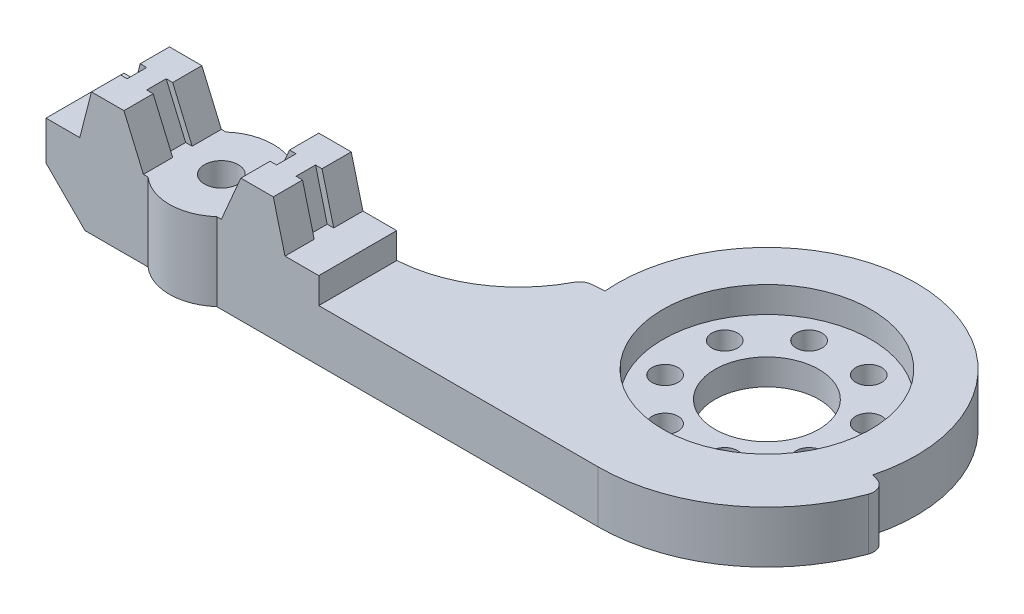
SolidWorks part; units mm, degrees
material "ABS"
ref_plane "正面" through (0, 0, 0) normal (0, 0, 1) x (1, 0, 0)
ref_plane "平面" through (0, 0, 0) normal (0, 1, 0) x (1, 0, 0)
ref_plane "右側面" through (0, 0, 0) normal (1, 0, 0) x (0, 0, -1)
sketch "ｽｹｯﾁ1" plane through (0, 0, 0) normal (0, 1, 0) x (1, 0, 0)
  line L0 (19, 10) -> (19, 3)
  line L1 (-10.5, 3) -> (32, 3)
  line L2 (-10.5, 3) -> (-10.5, -3)
  line L3 (-10.5, -3) -> (32, -3)
  line L4 (32, 3) -> (32, -3)
  line L5 (-10.5, 3) -> (32, -3) construction
  line L6 (-10.5, -3) -> (32, 3) construction
  line L7 (32, 10) -> (19.0495, 8.867)
  line L8 (32, 10) -> (44.557, 6.6354)
  line L9 (19.0495, 8.867) -> (17.1765, 8.7031)
  circle A0 centre (32, 10) radius 13
  circle A1 centre (32, 10) radius 11.5
  point P4 (10.75, 0)
  dimension "D5" = 26
  dimension "D6" = 23
  dimension "D1" = 6
  dimension "D2" = 3
  dimension "D3" = 10.5
  dimension "D4" = 32
  dimension "D7" = 5
  dimension "D8" = 15
extrude "ﾎﾞｽ - 押し出し1" add sketch "ｽｹｯﾁ1" along normal blind 4 contours A0 L1 L2 L3 | A0 L9 L0 L1 | A1 L7 A0 L1 | L4 A1 L8 L7 L1 | L8 A1 L7 | L1 A1 L4 | A1 L1 A0 L4 | A1 L4 A0 L8 region at (19.6068, 0, -4.7032) region at (20.6203, 0, -5.8719) region at (6.9791, 0, 0.1211) region at (39.8161, 0, 0.1861) region at (32.377, 0, -14.3095) region at (32.0912, 0, -5.2465) region at (26.5286, 0, 0.4611) region at (28.4673, 0, -1.1659)
fillet "ﾌｨﾚｯﾄ1" radius 10 1 edges at (19, 2, -3)
fillet "ﾌｨﾚｯﾄ2" radius 1 2 edges at (44.557, 2, -6.6354) (19, 2, -8.8626)
sketch "ｽｹｯﾁ2" plane through (0, 4, 0) normal (0, 1, 0) x (1, 0, 0)
  line L0 (-10.5, 3) -> (9.896, 3) construction
  line L1 (-10.5, -3) -> (10.5, -3)
  line L2 (-10.5, -3) -> (-10.5, 3)
  line L3 (-10.5, 3) -> (10.5, 3)
  line L4 (10.5, -3) -> (10.5, 3)
  line L5 (-10.5, -3) -> (10.5, 3) construction
  line L6 (-10.5, 3) -> (10.5, -3) construction
  point P4 (0, 0)
  dimension "D1" = 21
extrude "ﾎﾞｽ - 押し出し2" add sketch "ｽｹｯﾁ2" along normal blind 2
sketch "ｽｹｯﾁ3" plane through (0, 6, 0) normal (0, 1, 0) x (1, 0, 0)
  circle A0 centre (0, 0) radius 4
  dimension "D1" = 8
extrude "ﾎﾞｽ - 押し出し3" add sketch "ｽｹｯﾁ3" against normal up to surface (6 mm away) up to face at (21.4165, 0, -5.634)
hole_wizard "M2 丸平ねじ用座ぐり穴1" positions "ｽｹｯﾁ4" profile "ｽｹｯﾁ5" counterbore size "M2" standard "JIS" end condition up to next
sketch "ｽｹｯﾁ4" plane through (0, 0, 0) normal (0, -1, 0) x (-1, 0, 0)
  point P0 (0, 0)
sketch "ｽｹｯﾁ5" plane through (0, 0, 0) normal (1, 0, 0) x (0, 0, -1)
  line L0 (0, 0) -> (0, 6)
  line L1 (0, 6) -> (1.3, 6)
  line L3 (1.3, 6) -> (1.3, 2)
  line L4 (1.3, 2) -> (3.1, 2)
  line L5 (3.1, 2) -> (3.1, 0)
  line L7 (3.1, 0) -> (0, 0)
  line L11 (0, -6.35) -> (0, 107.95) construction
  dimension "通し穴の直径" = 2.6
  dimension "通し穴の深さ" = 6
  dimension "座ぐり穴の直径" = 6.2
  dimension "座ぐり穴の深さ" = 2
chamfer "面取り1" distance 3 angle 45 1 edges at (-10.5, 0, 0)
sketch "ｽｹｯﾁ6" plane through (0, 0, 3) normal (0, 0, 1) x (1, 0, 0)
  line L0 (3, 6) -> (4.5, 9.5)
  line L1 (2.6458, 6) -> (10.5, 6) construction
  line L2 (4.5, 9.5) -> (7, 9.5)
  line L3 (7, 9.5) -> (7.9, 6)
  line L4 (7.9, 6) -> (3, 6)
  dimension "D1" = 3.5
  dimension "D2" = 3
  dimension "D3" = 2.5
  dimension "D4" = 7
  dimension "D5" = 7.9
extrude "ﾎﾞｽ - 押し出し4" add sketch "ｽｹｯﾁ6" against normal up to surface (6 mm away) up to face at (7.6806, 3.3333, -3)
sketch "ｽｹｯﾁ10" plane through (0, 0, 0) normal (0, 0, 1) x (1, 0, 0)
  line L0 (5, 9.5) -> (4.5, 9.5)
  line L1 (5, 9.5) -> (3.5, 6)
  line L2 (4.5, 9.5) -> (3, 6)
  line L3 (3.5, 6) -> (3, 6)
  line L4 (5, 9.5) -> (3, 6) construction
  line L5 (4.5, 9.5) -> (3.5, 6) construction
  line L6 (7, 9.5) -> (4.5, 9.5) construction
  line L7 (6.5, 9.5) -> (7, 9.5)
  line L8 (6.5, 9.5) -> (7.4, 6)
  line L9 (7, 9.5) -> (7.9, 6)
  line L10 (7.4, 6) -> (7.9, 6)
  line L11 (6.5, 9.5) -> (7.9, 6) construction
  line L12 (7, 9.5) -> (7.4, 6) construction
  point P5 (4, 7.75)
  point P14 (7.2, 7.75)
  dimension "D1" = 0.5
extrude "ｶｯﾄ - 押し出し2" cut sketch "ｽｹｯﾁ10" against normal mid plane 1.5
mirror "ﾐﾗｰ1" about plane through (0, 0, 0) normal (1, 0, 0) of "ｶｯﾄ - 押し出し2", "ﾎﾞｽ - 押し出し4"
hole_wizard "M2 丸平ねじ用座ぐり穴2" positions "ｽｹｯﾁ7" profile "ｽｹｯﾁ8" counterbore size "M2" standard "JIS" end condition up to next
sketch "ｽｹｯﾁ7" plane through (0, 4, 0) normal (0, 1, 0) x (1, 0, 0)
  point P0 (32, 10)
sketch "ｽｹｯﾁ8" plane through (32, 4, -10) normal (1, 0, 0) x (0, 0, 1)
  line L0 (0, 0) -> (0, 4)
  line L1 (0, 4) -> (4, 4)
  line L3 (4, 4) -> (4, 2)
  line L4 (4, 2) -> (8, 2)
  line L5 (8, 2) -> (8, 0)
  line L7 (8, 0) -> (0, 0)
  line L11 (0, -6.35) -> (0, 107.95) construction
  dimension "通し穴の直径" = 8
  dimension "通し穴の深さ" = 4
  dimension "座ぐり穴の直径" = 16
  dimension "座ぐり穴の深さ" = 2
sketch "ｽｹｯﾁ9" plane through (0, 2, 0) normal (0, 1, 0) x (1, 0, 0)
  line L0 (29.7039, 15.5433) -> (32, 10) construction
  line L1 (32, 10) -> (32, 15.9574) construction
  circle A0 centre (29.7039, 15.5433) radius 1
  dimension "D1" = 2
  dimension "D2" = 6
  dimension "D3" = 22.5
extrude "ｶｯﾄ - 押し出し1" cut sketch "ｽｹｯﾁ9" against normal blind 2
pattern_circular "円形ﾊﾟﾀｰﾝ1" count 8 over 360 about axis through (32, 4, -10) along (0, 1, 0) of "ｶｯﾄ - 押し出し1" reverse direction yes
